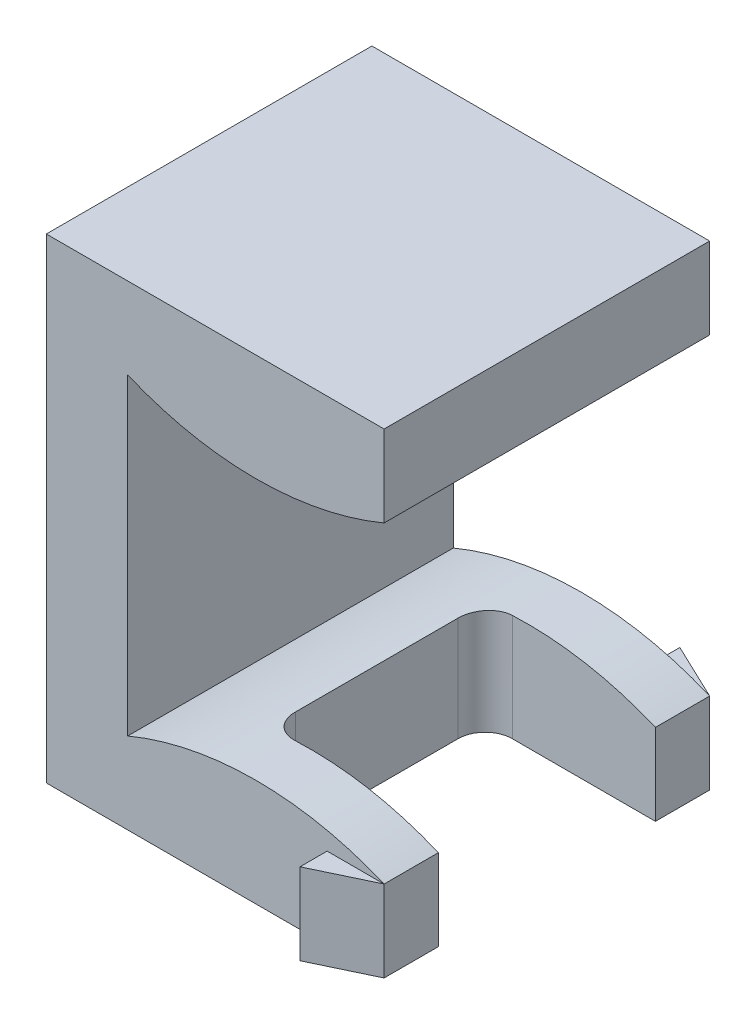
SolidWorks part; units mm, degrees
ref_plane "Front Plane" through (0, 0, 0) normal (0, 0, 1) x (1, 0, 0)
ref_plane "Top Plane" through (0, 0, 0) normal (0, 1, 0) x (1, 0, 0)
ref_plane "Right Plane" through (0, 0, 0) normal (1, 0, 0) x (0, 0, -1)
sketch "Sketch1" plane through (0, 0, 0) normal (0, 0, 1) x (1, 0, 0)
  line L2 (-159.7982, 8.7625) -> (-172.2482, 8.7625)
  line L3 (-172.2482, 8.7625) -> (-172.2482, -8.7625)
  line L7 (-169.2482, -22.8519) -> (-169.2482, 5.7625) construction
  line L12 (-169.2482, 4.7625) -> (-169.2482, 1.5875) construction
  line L23 (-159.7982, 5.7625) -> (-159.7982, 8.7625)
  line L28 (-164.5232, 4.8125) -> (-144.5007, 4.8125) construction
  line L29 (-156.5482, 4.7625) -> (-169.2482, 4.7625) construction
  line L30 (-169.2482, 5.7625) -> (-169.2482, 4.7625)
  line L32 (-158.1026, 4.7625) -> (-158.1026, -4.7625) construction
  line L33 (-169.2482, -4.7625) -> (-156.5482, -4.7625) construction
  line L34 (-169.2482, 4.7625) -> (-169.2482, -4.7625)
  line L35 (-172.2482, 0) -> (-169.2482, 0) construction
  line L36 (-169.2482, -5.7625) -> (-169.2482, -4.7625)
  line L37 (-159.7982, -5.7625) -> (-159.7982, -8.7625)
  line L38 (-159.7982, -8.7625) -> (-172.2482, -8.7625)
  line L39 (-159.7982, 4.7625) -> (-159.7982, 1.5875) construction
  arc A5 (-169.2482, 5.7625) -> (-159.7982, 5.7625) centre (-164.5232, 17.0378) ccw
  arc A6 (-169.2482, -5.7625) -> (-159.7982, -5.7625) centre (-164.5232, -17.0378) cw
  point P18 (-158.1026, 0)
  dimension "D4" = 3
  dimension "D3" = 3
  dimension "D1" = 0.05
  dimension "D2" = 1
extrude "MainBody" add sketch "Sketch1" along normal mid plane 12
sketch "Sketch3" plane through (0, -8.7625, 0) normal (0, -1, 0) x (1, 0, 0)
  line L0 (-159.7982, -6) -> (-161.8982, -7)
  line L1 (-161.8982, -7) -> (-161.8982, -6)
  line L2 (-172.2482, -6) -> (-159.7982, -6) construction
  line L3 (-161.8982, -6) -> (-159.7982, -6)
  line L4 (-162.8982, -12.7) -> (-162.8982, -6.35) construction
  line L5 (6.8475, 0) -> (-6.8475, 0) construction
  line L6 (-161.8982, 6) -> (-159.7982, 6)
  line L7 (-161.8982, 7) -> (-161.8982, 6)
  line L8 (-159.7982, 6) -> (-161.8982, 7)
  dimension "D1" = 1
  dimension "D2" = 1
extrude "Hook" add sketch "Sketch3" against normal up to vertex (3 mm away) up to point (-159.7982, -5.7625, -6)
sketch "Sketch4" plane through (0, -8.7625, 0) normal (0, -1, 0) x (1, 0, 0)
  line L0 (-159.7982, 6) -> (-159.7982, -6) construction
  line L1 (-159.7982, 4) -> (-166.0732, 4)
  line L2 (-159.7982, 4) -> (-159.7982, -4)
  line L3 (-159.7982, -4) -> (-166.0732, -4)
  line L4 (-166.0732, 4) -> (-166.0732, -4)
  line L5 (-172.2482, 6) -> (-172.2482, -6) construction
  line L6 (-172.2482, -6) -> (-161.8982, -6) construction
  line L7 (-162.8982, -6.35) -> (-169.2482, -6.35) construction
  point P6 (-166.0732, 0)
  point P9 (-172.2482, 0)
  point P14 (-166.0732, -6.35)
  dimension "D1" = 2
extrude "Flex" cut sketch "Sketch4" against normal up to next
fillet "Fillet1" radius 1 2 edges at (-166.0732, -6.8368, -4) (-166.0732, -6.8368, 4)
equation "\"HookThickness\"=3"
equation "\"HookOverhang\"=3"
equation "\"HookHeight\"=5"
equation "\"D3@Sketch1\"=\"HookThickness\""
equation "\"D4@Sketch1\"=\"HookThickness\""
